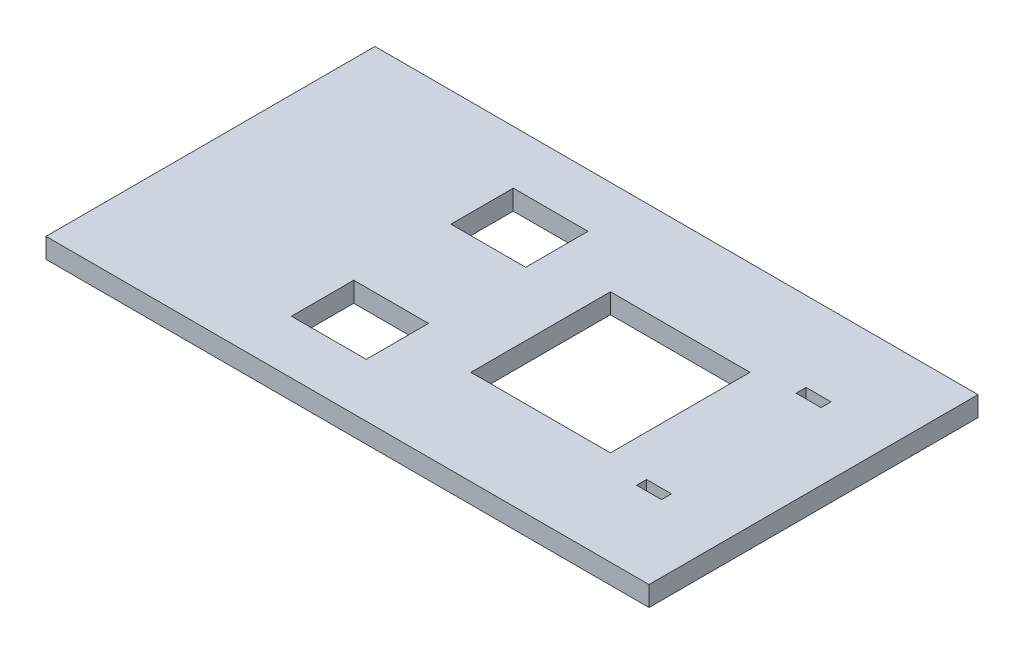
SolidWorks part; units mm, degrees
material "Maple"
ref_plane "Front Plane" through (0, 0, 0) normal (0, 0, 1) x (1, 0, 0)
ref_plane "Top Plane" through (0, 0, 0) normal (0, 1, 0) x (1, 0, 0)
ref_plane "Right Plane" through (0, 0, 0) normal (1, 0, 0) x (0, 0, -1)
sketch "Sketch1" plane through (0, 0, 0) normal (0, 1, 0) x (1, 0, 0)
  line L1 (0, 0) -> (121, 0)
  line L2 (0, 0) -> (0, -66)
  line L3 (0, -66) -> (121, -66)
  line L4 (121, 0) -> (121, -66)
  dimension "D1" = 121
  dimension "D2" = 66
extrude "Boss-Extrude1" add sketch "Sketch1" along normal blind 4
sketch "Sketch2" plane through (0, 4, 0) normal (0, 1, 0) x (1, 0, 0)
  line L0 (0, -33) -> (121, -33) construction
  line L1 (0, 0) -> (0, -66) construction
  line L2 (121, -66) -> (121, 0) construction
  line L3 (46, 0) -> (46, -66) construction
  line L4 (121, 0) -> (0, 0) construction
  line L5 (0, -66) -> (121, -66) construction
  line L7 (66.25, -19) -> (94.25, -19)
  line L8 (66.25, -19) -> (66.25, -47)
  line L9 (66.25, -47) -> (94.25, -47)
  line L10 (94.25, -19) -> (94.25, -47)
  line L11 (66.25, -19) -> (94.25, -47) construction
  line L12 (66.25, -47) -> (94.25, -19) construction
  line L13 (38.5, -23.25) -> (53.5, -23.25)
  line L14 (38.5, -23.25) -> (38.5, -10.75)
  line L15 (38.5, -10.75) -> (53.5, -10.75)
  line L16 (53.5, -23.25) -> (53.5, -10.75)
  line L17 (38.5, -23.25) -> (53.5, -10.75) construction
  line L18 (38.5, -10.75) -> (53.5, -23.25) construction
  line L19 (38.5, -55.25) -> (53.5, -55.25)
  line L20 (38.5, -55.25) -> (38.5, -42.75)
  line L21 (38.5, -42.75) -> (53.5, -42.75)
  line L22 (53.5, -55.25) -> (53.5, -42.75)
  line L23 (38.5, -55.25) -> (53.5, -42.75) construction
  line L24 (38.5, -42.75) -> (53.5, -55.25) construction
  circle A0 centre (46, -17) radius 3.5 construction
  circle A1 centre (46, -49) radius 3.5 construction
  point P16 (80.25, -33)
  dimension "D1" = 7
  dimension "D2" = 32
  dimension "D3" = 16
  dimension "D4" = 46
  dimension "D5" = 28
  dimension "D6" = 28
  dimension "D7" = 40.75
  dimension "D8" = 12.5
  dimension "D9" = 15
  dimension "D10" = 15
  dimension "D11" = 12.5
extrude "Cut-Extrude1" cut sketch "Sketch2" against normal through all
sketch "Sketch3" plane through (0, 0, 0) normal (0, -1, 0) x (1, 0, 0)
  line L1 (107.5, 50) -> (102.5, 50)
  line L2 (107.5, 50) -> (107.5, 48)
  line L3 (107.5, 48) -> (102.5, 48)
  line L4 (102.5, 50) -> (102.5, 48)
  line L5 (102.5, 16) -> (107.5, 16)
  line L6 (102.5, 16) -> (102.5, 18)
  line L7 (102.5, 18) -> (107.5, 18)
  line L8 (107.5, 16) -> (107.5, 18)
extrude "Cut-Extrude2" cut sketch "Sketch3" against normal through all
equation "\"D3@Sketch2\"=\"D2@Sketch2\"/2"
equation "\"D11@Sketch2\"=\"D8@Sketch2\""
equation "\"D10@Sketch2\"=\"D9@Sketch2\""
